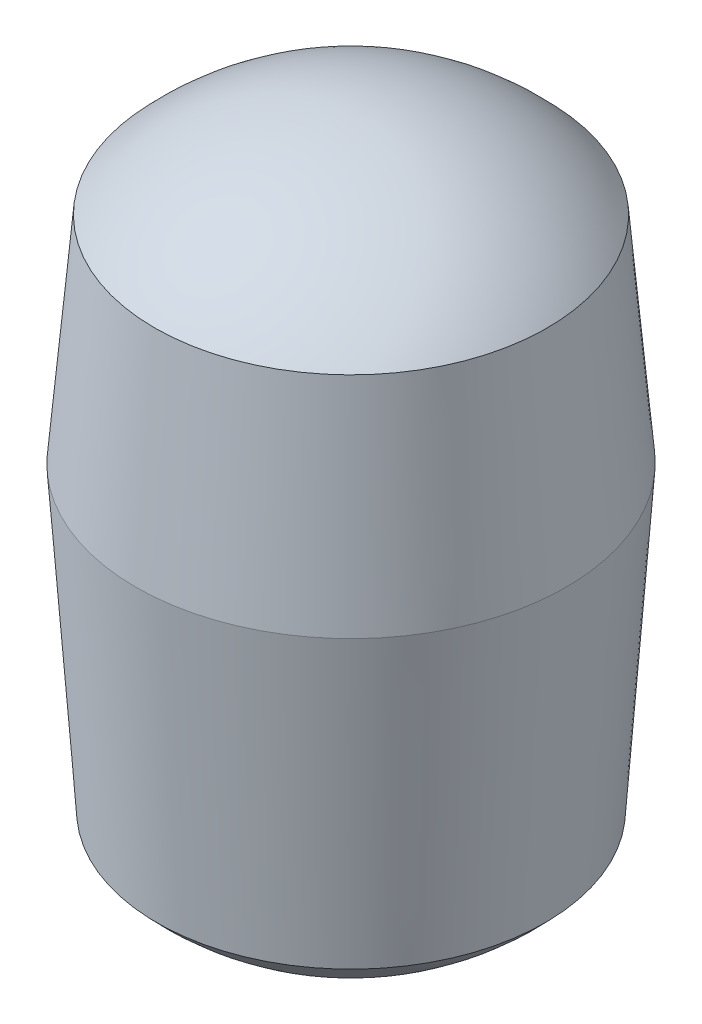
SolidWorks part; units mm, degrees
ref_plane "Front Plane" through (0, 0, 0) normal (0, 0, 1) x (1, 0, 0)
ref_plane "Top Plane" through (0, 0, 0) normal (0, 1, 0) x (1, 0, 0)
ref_plane "Right Plane" through (0, 0, 0) normal (1, 0, 0) x (0, 0, -1)
sketch "Sketch1" plane through (0, 0, 0) normal (0, 1, 0) x (1, 0, 0)
  circle A0 centre (0, 0) radius 0.5
  dimension "D1" = 1
extrude "Boss-Extrude1" add sketch "Sketch1" along normal blind 0.5 draft 5
dome "Dome1" faces to dome 1 distance 0.2 reverse direction no elliptical dome no face at (0, 0.5, 0.4563) parameters "D1"=0.2
sketch "Sketch2" plane through (0, 0, 0) normal (0, -1, 0) x (1, 0, 0)
  circle A0 centre (0, 0) radius 0.5
extrude "Boss-Extrude2" add sketch "Sketch2" along normal blind 0.7 draft 4
dome "Dome3" faces to dome 1 distance 0.2 reverse direction no elliptical dome no face at (0, -0.7, -0.4511) parameters "D1"=0.2
